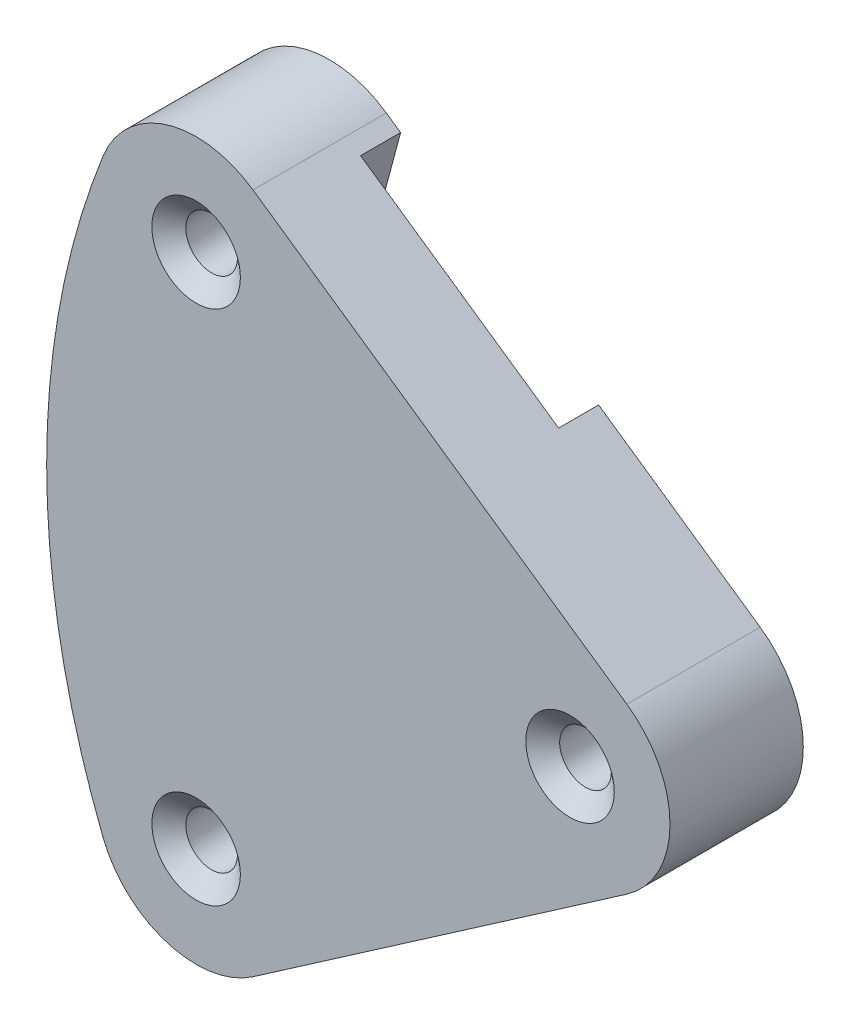
SolidWorks part; units mm, degrees
material "PET"
ref_plane "Front Plane" through (0, 0, 0) normal (0, 0, 1) x (1, 0, 0)
ref_plane "Top Plane" through (0, 0, 0) normal (0, 1, 0) x (1, 0, 0)
ref_plane "Right Plane" through (0, 0, 0) normal (1, 0, 0) x (0, 0, -1)
sketch "Sketch1" plane through (0, 0, 0) normal (0, 0, 1) x (1, 0, 0)
  line L0 (-33.2997, 0) -> (33.2997, 0) construction
  line L1 (33.2997, 0) -> (-33.2997, 46.0375)
  line L2 (-33.2997, 46.0375) -> (-33.2997, -46.0375)
  line L3 (33.2997, 0) -> (-33.2997, -46.0375)
  point P4 (0, 0)
  dimension "D1" = 80.9625
  dimension "D2" = 46.0375
extrude "Boss-Extrude1" add sketch "Sketch1" along normal blind 12.7
sketch "Sketch2" plane through (0, 0, 12.7) normal (0, 0, 1) x (1, 0, 0)
  line L0 (-33.2997, 0) -> (33.2997, 0) construction
  line L1 (-33.2997, 46.0375) -> (-33.2997, -46.0375) construction
  circle A0 centre (42.9003, 0) radius 76.2
  circle A2 centre (42.9003, 0) radius 101.6
  dimension "D1" = 152.4
  dimension "D2" = 25.4
extrude "Cut-Extrude1" cut sketch "Sketch2" against normal through all
fillet "Fillet1" radius 9.525 3 edges at (-22.7246, 38.7274, 6.35) (33.2997, 0, 6.35) (-22.7246, -38.7274, 6.35)
hole_wizard "CSK for #8 Flat Head Machine Screw (100)1" positions "Sketch3" profile "Sketch4" countersink size "#8" standard "ANSI Inch" end condition up to next
sketch "Sketch3" plane through (0, 0, 12.7) normal (0, 0, 1) x (1, 0, 0)
  point P0 (-19.0637, -24.6175)
  point P2 (-19.0637, 24.6175)
  point P4 (16.5488, 0)
sketch "Sketch4" plane through (-19.0637, -24.6175, 12.7) normal (1, 0, 0) x (0, -1, 0)
  line L0 (0, 0) -> (0, 12.7)
  line L1 (0, 12.7) -> (2.4574, 12.7)
  line L2 (2.4574, 12.7) -> (2.4574, 1.4759)
  line L3 (2.4574, 1.4759) -> (4.2164, 0)
  line L5 (4.2164, 0) -> (0, 0)
  line L6 (-2.4574, 1.4759) -> (-4.2164, 0) construction
  line L11 (0, -6.35) -> (0, 107.95) construction
  dimension "Thru Hole Dia." = 4.9149
  dimension "Thru Hole Depth" = 12.7
  dimension "Near C'Sink Dia." = 8.4328
  dimension "Near C'Sink Angle" = 100
sketch "Sketch5" plane through (0, 0, 0) normal (0, 0, -1) x (-1, 0, 0)
  line L0 (33.2997, 0) -> (-16.5488, 0) construction
  line L1 (30.8235, 19.2674) -> (-18.1923, 6.1336)
  line L2 (-16.5488, 0) -> (-22.8988, 0) construction
  line L3 (30.8235, -19.2674) -> (-18.1923, -6.1336)
  arc A0 (-18.1923, 6.1336) -> (-18.1923, -6.1336) centre (-16.5488, 0) ccw
  arc A1 (27.9157, -28.1343) -> (27.9157, 28.1343) centre (-42.9003, 0) ccw construction
  arc A2 (30.8235, -19.2674) -> (30.8235, 19.2674) centre (-42.9003, 0) ccw
  dimension "D1" = 12.7
  dimension "D2" = 15
extrude "Cut-Extrude2" cut sketch "Sketch5" against normal blind 6.35
sketch "Sketch6" plane through (0, 0, 0) normal (0, 0, -1) x (-1, 0, 0)
  line L0 (16.5887, -15.4532) -> (-4.2656, -9.8653)
  line L1 (16.5887, -15.4532) -> (11.9869, -32.6273)
  line L2 (-4.2656, -9.8653) -> (-8.8674, -27.0394)
  line L3 (11.9869, -32.6273) -> (-8.8674, -27.0394)
  line L4 (-18.1923, -6.1336) -> (30.8235, -19.2674) construction
  line L5 (33.2997, 0) -> (-26.0738, 0) construction
  line L6 (11.9869, 32.6273) -> (-8.8674, 27.0394)
  line L7 (-4.2656, 9.8653) -> (-8.8674, 27.0394)
  line L8 (16.5887, 15.4532) -> (11.9869, 32.6273)
  line L9 (16.5887, 15.4532) -> (-4.2656, 9.8653)
  arc A1 (30.8235, -19.2674) -> (30.8235, 19.2674) centre (-42.9003, 0) ccw construction
  arc A2 (-21.965, 7.8352) -> (-21.965, -7.8352) centre (-16.5488, 0) ccw construction
  dimension "D2" = 21.59
  dimension "D3" = 17.78
extrude "Cut-Extrude3" cut sketch "Sketch6" against normal blind 3.81
sketch "Sketch7" plane through (0, 0, 6.35) normal (0, 0, -1) x (-1, 0, 0)
  line L0 (33.2997, 0) -> (0, 0) construction
  circle A0 centre (21.4797, -10.1897) radius 1.397
  arc A1 (30.8235, -19.2674) -> (30.8235, 19.2674) centre (-42.9003, 0) ccw construction
  circle A2 centre (21.4797, 10.1897) radius 1.397
  dimension "D1" = 2.794
extrude "Cut-Extrude4" cut sketch "Sketch7" against normal blind 3.175
hole_wizard "Hole1" positions "Sketch8" profile "Sketch9" legacy
sketch "Sketch8" plane through (0, 0, 3.81) normal (0, 0, -1) x (-1, 0, 0)
  line L0 (0, 0) -> (-16.5488, 0) construction
  point P0 (8.9047, -20.0866)
  point P3 (-0.1363, -17.6641)
  point P12 (-0.1363, 17.6641)
  point P13 (8.9047, 20.0866)
sketch "Sketch9" plane through (-8.9047, -20.0866, 3.81) normal (1, 0, 0) x (0, 1, 0)
  line L0 (0, 0) -> (0, 2.921)
  line L1 (0, 2.921) -> (1.4986, 2.921)
  line L2 (1.4986, 2.921) -> (1.6383, 0)
  line L3 (1.6383, 0) -> (0, 0)
  line L4 (0, 110) -> (0, -10) construction
  dimension "Minor Diameter" = 2.9972
  dimension "Depth" = 2.921
  dimension "Major Diameter" = 3.2766
hole_wizard "#2 Clearance Hole1" positions "Sketch10" profile "Sketch11" hole size "#2" standard "ANSI Inch"
sketch "Sketch10" plane through (0, 0, 3.81) normal (0, 0, -1) x (-1, 0, 0)
  line L0 (0, 0) -> (-42.9003, 0) construction
  point P0 (8.9047, -20.0866)
  point P3 (-0.1363, -17.6641)
  point P17 (-0.1363, 17.6641)
  point P18 (8.9047, 20.0866)
sketch "Sketch11" plane through (-8.9047, -20.0866, 3.81) normal (1, 0, 0) x (0, 1, 0)
  line L0 (0, 0) -> (0, 4.7625)
  line L1 (0, 4.7625) -> (1.3525, 4.7625)
  line L2 (1.3525, 4.7625) -> (1.3525, 0)
  line L5 (1.3525, 0) -> (0, 0)
  line L10 (0, 4.7625) -> (-1.3526, 4.7625) construction
  line L11 (0, -6.35) -> (0, 107.95) construction
  dimension "Hole Dia." = 2.7051
  dimension "Hole Depth" = 4.7625
  dimension "Drill Angle" = 180
